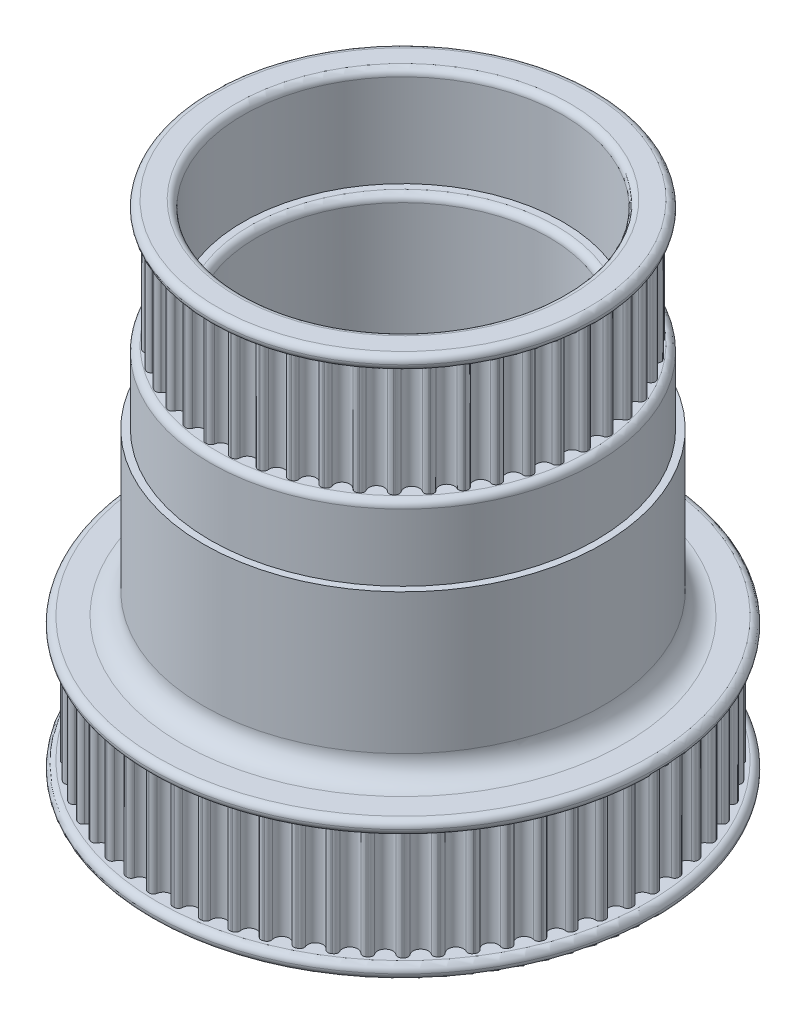
SolidWorks part; units mm, degrees
ref_plane "Front Plane" through (0, 0, 0) normal (0, 0, 1) x (1, 0, 0)
ref_plane "Top Plane" through (0, 0, 0) normal (0, 1, 0) x (1, 0, 0)
ref_plane "Right Plane" through (0, 0, 0) normal (1, 0, 0) x (0, 0, -1)
sketch "PulleyOffsets" plane through (0, 0, 0) normal (1, 0, 0) x (0, 0, -1)
  line L0 (21.0344, 0) -> (-21.0344, 0) construction
  line L1 (21.0344, 42.0687) -> (-21.0344, 42.0687) construction
  line L2 (0, 0) -> (0, 42.0688) construction
  point P7 (0, 0)
  dimension "D1" = 42.0688
ref_axis "Axis1" through (0, 34.9332, 0) along (0, -1, 0)
ref_plane "Big Pulley Plane" through (0, 0, 0) normal (0, 1, 0) x (1, 0, 0)
ref_plane "Small Pulley Plane" through (0, 42.0688, 0) normal (0, 1, 0) x (1, 0, 0)
sketch "Sketch1" plane through (0, 0, 0) normal (0, 1, 0) x (1, 0, 0)
  line L0 (0, 0) -> (0, 28.2667) construction
  line L1 (0, 0) -> (2.9202, 27.7837) construction
  circle A0 centre (0, 0) radius 28.2667 construction
  circle A1 centre (0, 0) radius 27.0467 construction
  circle A2 centre (0, 27.9367) radius 0.89 construction
  circle A5 centre (2.9202, 27.7837) radius 0.89 construction
  arc A6 (0, 27.0467) -> (0.8804, 27.8061) centre (0, 27.9367) ccw
  arc A7 (0.8804, 27.8061) -> (1.3997, 28.2321) centre (1.3749, 27.7327) cw
  arc A8 (1.559, 28.2237) -> (2.031, 27.7458) centre (1.5314, 27.7245) cw
  arc A9 (2.8272, 26.8986) -> (2.031, 27.7458) centre (2.9202, 27.7837) cw
  arc A10 (1.3997, 28.2321) -> (1.559, 28.2237) centre (0, 0) cw
  arc A11 (0, 27.0467) -> (2.8272, 26.8986) centre (0, 0) ccw
  dimension "D1" = 56.5335
  dimension "D3" = 1.78
  dimension "D4" = 0.5
  dimension "D2" = 1.22
  dimension "D5" = 6
extrude "Boss-Extrude1" add sketch "Sketch1" along normal mid plane 13 contours A6 A11 A9 A8 A7 region at (0.001, 0, -0.0192)
pattern_circular "CirPattern1" count 60 over 360 about axis through (0, 34.9332, 0) along (0, -1, 0) of "Boss-Extrude1"
sketch "Sketch2" plane through (0, 0, 0) normal (1, 0, 0) x (0, 0, -1)
  line L10 (0, 6.5) -> (29.4415, 6.5) construction
  line L11 (0, 6.5) -> (0, 8.0875) construction
  line L12 (0, 8.0875) -> (29.4415, 8.0875) construction
  line L15 (29.4415, 6.5) -> (29.4415, 8.0875) construction
  line L20 (0, 34.9332) -> (0, -6.9932) construction
  line L22 (29.4415, 8.0875) -> (0, 8.0875)
  line L23 (29.4415, 8.0875) -> (29.4415, 6.5)
  line L24 (29.4415, 6.5) -> (0, 6.5)
  line L25 (0, 8.0875) -> (0, 6.5)
  dimension "D1" = 1.5875
  dimension "D2" = 29.4415
  dimension "D3" = 6.5
revolve "Revolve3" add sketch "Sketch2" angle 360 about axis through (0, 34.9332, 0) along (0, -1, 0) region at (0, 7.2937, -14.7207)
mirror "Mirror1" about plane through (0, 0, 0) normal (0, 1, 0) of "Revolve3"
sketch "Sketch6" plane through (0, 0, 0) normal (0, 1, 0) x (1, 0, 0)
  line L0 (0, 0) -> (0, 21.582) construction
  line L1 (0, 0) -> (2.8938, 21.0541) construction
  circle A0 centre (0, 0) radius 21.582 construction
  circle A1 centre (0, 0) radius 20.362 construction
  circle A2 centre (0, 21.252) radius 0.89 construction
  circle A5 centre (2.8938, 21.0541) radius 0.89 construction
  arc A6 (0, 20.362) -> (0.8793, 21.1145) centre (0, 21.252) ccw
  arc A7 (0.8793, 21.1145) -> (1.4059, 21.5362) centre (1.3733, 21.0373) cw
  arc A8 (1.5397, 21.527) -> (2.004, 21.0376) centre (1.5041, 21.0283) cw
  arc A9 (2.7726, 20.1724) -> (2.004, 21.0376) centre (2.8938, 21.0541) cw
  arc A10 (1.4059, 21.5362) -> (1.5397, 21.527) centre (0, 0) cw construction
  arc A11 (0, 20.362) -> (2.7726, 20.1724) centre (0, 0) ccw
  arc A12 (1.4059, 21.5362) -> (1.5397, 21.527) centre (0, 0) cw
  dimension "D3" = 1.78
  dimension "D4" = 0.5
  dimension "D2" = 1.22
  dimension "D1" = 43.1641
  dimension "D5" = 7.826
extrude "Boss-Extrude2" add sketch "Sketch6" along normal mid plane 13 from surface contours A6 A11 A9 A8 A7 region at (0.0017, 0, -0.025) starting at plane "Small Pulley Plane"
pattern_circular "CirPattern2" count 46 over 360 about axis through (0, 34.9332, 0) along (0, -1, 0) of "Boss-Extrude2"
sketch "Sketch9" plane through (0, 0, 0) normal (1, 0, 0) x (0, 0, -1)
  line L1 (0, 35.5688) -> (22.7568, 35.5688)
  line L2 (0, 35.5688) -> (0, 33.9813)
  line L3 (0, 33.9813) -> (22.7568, 33.9813)
  line L4 (22.7568, 35.5688) -> (22.7568, 33.9813)
  line L6 (0, 48.5687) -> (22.7568, 48.5687)
  line L7 (0, 48.5687) -> (0, 50.1562)
  line L8 (0, 50.1562) -> (22.7568, 50.1562)
  line L9 (22.7568, 48.5687) -> (22.7568, 50.1562)
  line L10 (29.4415, 8.0875) -> (29.4415, 6.5) construction
  line L11 (0, 34.9332) -> (0, -6.9932) construction
  line L12 (21.1145, 48.5687) -> (20.362, 48.5687) construction
  line L13 (20.1641, 35.5688) -> (21.0376, 35.5688) construction
  dimension "D1" = 22.7568
revolve "Revolve4" add sketch "Sketch9" angle 360 about axis through (0, 34.9332, 0) along (0, -1, 0)
sketch "Sketch10" plane through (0, -8.0875, 0) normal (0, -1, 0) x (1, 0, 0)
  circle A0 centre (0, 0) radius 18.669
  dimension "D1" = 37.338
extrude "Cut-Extrude1" cut sketch "Sketch10" against normal through all
sketch "Sketch11" plane through (0, 50.1562, 0) normal (0, 1, 0) x (1, 0, 0)
  circle A0 centre (0, 0) radius 22.5
  dimension "D1" = 45
extrude "Cut-Extrude2" cut sketch "Sketch11" against normal up to surface (16.175 mm away) flip side to cut up to face at (0, 33.9813, 18.669)
sketch "Sketch12" plane through (0, 0, 0) normal (0, 0, 1) x (1, 0, 0)
  line L0 (29.4415, 8.0875) -> (-29.4415, 8.0875) construction
  line L1 (18.669, 33.9813) -> (22.5, 33.9813)
  line L2 (18.669, 33.9813) -> (18.669, 8.0875) construction
  line L3 (18.669, 8.0875) -> (22.5, 8.0875)
  line L4 (22.5, 33.9813) -> (22.5, 8.0875) construction
  line L5 (22.5, 33.9813) -> (22.5, 35.5688) construction
  line L6 (22.5, 26.9813) -> (22.5, 33.9813)
  line L7 (22.5, 26.9813) -> (23.2938, 26.9813)
  line L8 (22.5, 26.9813) -> (22.5, 8.0875) construction
  line L9 (22.5, 8.0875) -> (23.2938, 8.0875)
  line L10 (23.2938, 26.9813) -> (23.2938, 8.0875)
  line L11 (18.669, -8.0875) -> (18.669, 8.0875) construction
  line L12 (18.669, 2.0875) -> (17.0815, 2.0875)
  line L13 (18.669, 2.0875) -> (18.669, 38.5688) construction
  line L14 (18.669, 38.5688) -> (17.0815, 38.5688)
  line L15 (17.0815, 2.0875) -> (17.0815, 38.5688)
  line L16 (-29.4415, -8.0875) -> (29.4415, -8.0875) construction
  line L18 (18.669, 2.0875) -> (18.669, 8.0875)
  line L19 (18.669, 33.9813) -> (18.669, 38.5688)
  line L20 (32.3856, 42.0688) -> (-32.3856, 42.0688) construction
  dimension "D1" = 7
  dimension "D2" = 0.7937
  dimension "D3" = 10.175
  dimension "D5" = 1.5875
  dimension "D4" = 3.5
revolve "Revolve5" add sketch "Sketch12" angle 360 about axis through (0, 34.9332, 0) along (0, -1, 0)
fillet "Fillet1" radius 2.54 1 edges at (0, 8.0875, -23.2938)
fillet "Fillet2" radius 0.7937 11 edges at (0, 38.5688, 17.0815) (0, 50.1562, -18.669) (0, -8.0875, -18.669) (0, 2.0875, 17.0815) (0, -8.0875, 29.4415) (0, 8.0875, 29.4415) (0, 50.1562, 22.5) (0, 48.5687, 22.5) (0, 35.5688, -22.5) (0, 6.5, 29.4415) (0, -6.5, 29.4415)
equation "\"TEETH_NUM\"= 60"
equation "\"TOOTH_PITCH\"= 3mm"
equation "\"PITCH_LINE_OFFSET\"= .015in"
equation "\"DIAMETER_PER_GROOVE\"= \"OUTSIDE_DIAMETER\" / \"TEETH_NUM\" * 1in"
equation "\"PITCH_DIAMETER\"= ( ( \"TEETH_NUM\" * 3 - 1.31 ) / 3.1415 + .415 ) * 1mm"
equation "\"OUTSIDE_DIAMETER\"= \"PITCH_DIAMETER\" - \"PITCH_LINE_OFFSET\" * 2"
equation "\"D1@Sketch1\"=\"OUTSIDE_DIAMETER\""
equation "\"TOOTH_HEIGHT\"= 1.22mm"
equation "\"D2@Sketch1\"=\"TOOTH_HEIGHT\""
equation "\"TOOTH_DIAMETER\"= 1.78mm"
equation "\"INTERNAL_RADIUS\"= .5mm"
equation "\"D3@Sketch1\"=\"TOOTH_DIAMETER\""
equation "\"D5@Sketch1\"=360 / \"TEETH_NUM\""
equation "\"D4@Sketch1\"=\"INTERNAL_RADIUS\""
equation "\"D1@CirPattern1\"=\"TEETH_NUM\""
equation "\"BELT_GAP\"= 13mm"
equation "\"D2@Sketch2\"=\"PITCH_DIAMETER\"/2+1/32"
equation "\"D3@Sketch2\"=\"BELT_GAP\"/2"
equation "\"2_TEETH_NUM\"= 46"
equation "\"2_PITCH_DIAMETER\"= ( ( \"2_TEETH_NUM\" * 3 - 1.31 ) / 3.1415 + .415 ) * 1mm"
equation "\"2_OUTSIDE_DIAMETER\"= \"2_PITCH_DIAMETER\" - \"PITCH_LINE_OFFSET\" * 2"
equation "\"2_DIAMETER_PER_GROOVE\"= \"2_OUTSIDE_DIAMETER\" / \"2_TEETH_NUM\" * 1in"
equation "\"D5@Sketch6\"=360/\"2_TEETH_NUM\""
equation "\"D1@Sketch6\"=\"2_OUTSIDE_DIAMETER\""
equation "\"D2@Sketch6\"=\"TOOTH_HEIGHT\""
equation "\"D3@Sketch6\"=\"TOOTH_DIAMETER\""
equation "\"D4@Sketch6\"=\"INTERNAL_RADIUS\""
equation "\"2_BELT_GAP\"= 13mm"
equation "\"D1@CirPattern2\"=\"2_TEETH_NUM\""
equation "\"D1@Boss-Extrude2\"=\"2_BELT_GAP\""
equation "\"Pulley_OffSets\"= 1.75 - 3 / 32"
equation "\"D1@PulleyOffsets\" = \"Pulley_OffSets\""
equation "\"D1@Boss-Extrude1\"=\"BELT_GAP\""
equation "\"D1@Sketch9\"=\"2_PITCH_DIAMETER\"/2+1/32"
equation "\"bearing_hole_depth_arm_side\"= 7mm + .125in"
equation "\"D3@Sketch12\"=\"bearing_hole_depth_arm_side\""
